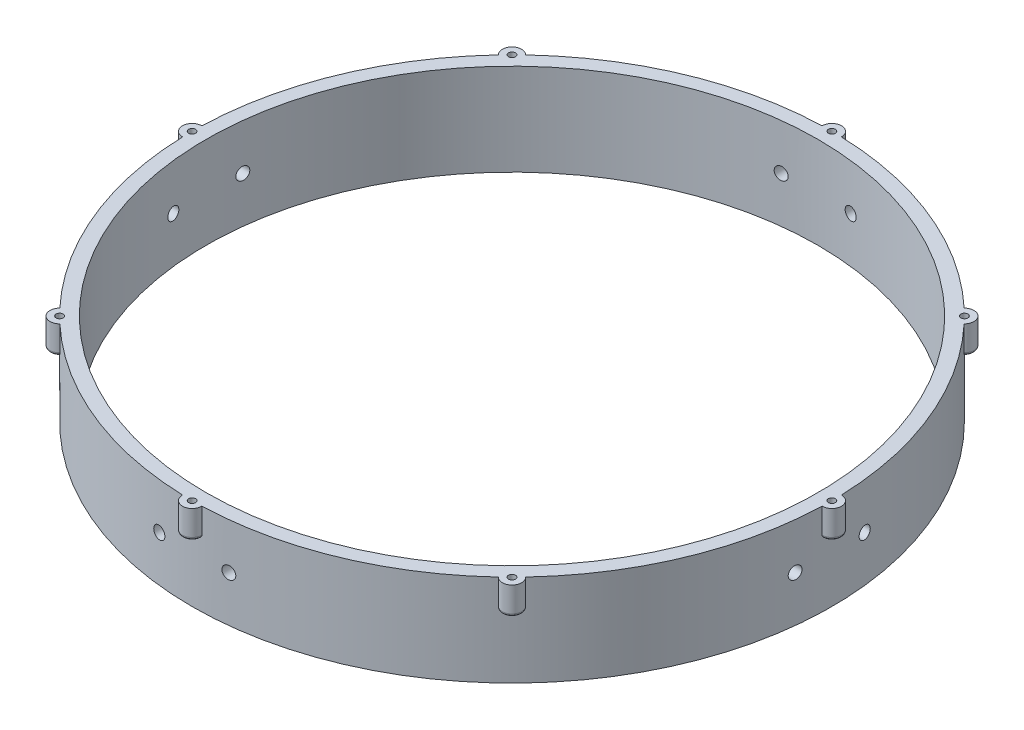
SolidWorks part; units mm, degrees
ref_plane "Front Plane" through (0, 0, 0) normal (0, 0, 1) x (1, 0, 0)
ref_plane "Top Plane" through (0, 0, 0) normal (0, 1, 0) x (1, 0, 0)
ref_plane "Right Plane" through (0, 0, 0) normal (1, 0, 0) x (0, 0, -1)
sketch "Sketch4" plane through (0, 0, 0) normal (0, 1, 0) x (1, 0, 0)
  line L0 (0, 0) -> (0, 53.2043) construction
  line L1 (0, 0) -> (37.6211, 37.6211) construction
  line L2 (0, 0) -> (53.2043, 0) construction
  line L3 (0, 0) -> (37.6211, -37.6211) construction
  line L4 (0, 0) -> (0, -53.2043) construction
  line L5 (0, 0) -> (-37.6211, -37.6211) construction
  line L6 (0, 0) -> (-53.2043, 0) construction
  line L7 (0, 0) -> (-37.6211, 37.6211) construction
  point P17 (0, 0)
  dimension "D1" = 8
ref_plane "Plane2" through (0, 0, 0) normal (0.7071, 0, -0.7071) x (-0.7071, 0, -0.7071)
sketch "Sketch1" plane through (0, 0, 0) normal (0, 1, 0) x (1, 0, 0)
  circle A0 centre (0, 0) radius 110
  circle A1 centre (0, 0) radius 115
  point P14 (0, 0)
  point P25 (0, 0)
  dimension "D1" = 220
extrude "ring extrusion" add sketch "Sketch1" along normal blind 33 contours A1 A0 | A0
sketch "marker holders sketch" plane through (0, 33, 0) normal (0, 1, 0) x (1, 0, 0)
  circle A0 centre (0, 115) radius 3.465
  circle A1 centre (0, 0) radius 115 construction
  dimension "D1" = 6.93
extrude "marker posts" add sketch "marker holders sketch" against normal blind 10
hole_wizard "Tap Drill for M3x0.5 Tap2" positions "3DSketch4" profile "Sketch10" hole size "M3x0.5" standard "ANSI Metric"
sketch3d "3DSketch4"
  point P0 (0, 33, -115)
sketch "Sketch10" plane through (0, 33, -115) normal (1, 0, 0) x (0, 0, 1)
  line L0 (0, 0) -> (0, 5.7511)
  line L1 (0, 5.7511) -> (1.25, 5)
  line L2 (1.25, 5) -> (1.25, 0)
  line L5 (1.25, 0) -> (0, 0)
  line L10 (0, 5.7511) -> (-1.25, 5) construction
  line L11 (0, -6.35) -> (0, 107.95) construction
  dimension "Hole Dia." = 2.5
  dimension "Hole Depth" = 5
  dimension "Drill Angle" = 118
fillet "Fillet1" radius 1 1 edges at (0, 23, -118.465)
pattern_circular "marker pattern" count 8 over 360 about axis through (0, 0, 0) along (0, 1, 0) of "marker posts", "Fillet1", "Tap Drill for M3x0.5 Tap2"
sketch "Sketch3" plane through (0, 0, 0) normal (0, 0, 1) x (1, 0, 0)
  line L0 (0, 0) -> (0, 33) construction
  line L1 (-12.5, 16.5) -> (12.5, 16.5) construction
  line L2 (110, 33) -> (-110, 33) construction
  line L3 (-110, 0) -> (110, 0) construction
  circle A0 centre (12.5, 16.5) radius 2.25
  circle A1 centre (-12.5, 16.5) radius 2.25
  point P11 (0, 16.5)
  point P13 (0, 16.5)
  dimension "D2" = 4.5
  dimension "D3" = 4.5
  dimension "D1" = 25
extrude "Cut-Extrude1" cut sketch "Sketch3" against normal through all
pattern_circular "CirPattern1" count 4 over 360 of "Cut-Extrude1"
equation "\"D1@Sketch1\"=\"outerD@ring assembly.Assembly\""
equation "\"D2@Sketch1\"=\"ringThick@ring assembly.Assembly\""
equation "\"D1@ring extrusion\"=\"ringH@ring assembly.Assembly\""
equation "\"D2@Sketch3\"= \"rodThick@ring assembly.Assembly\" + .5"
equation "\"D3@Sketch3\"= \"rodThick@ring assembly.Assembly\" + .5"
equation "\"D1@marker holders sketch\"=\"markerCapRad@ring assembly.Assembly\"*2"
